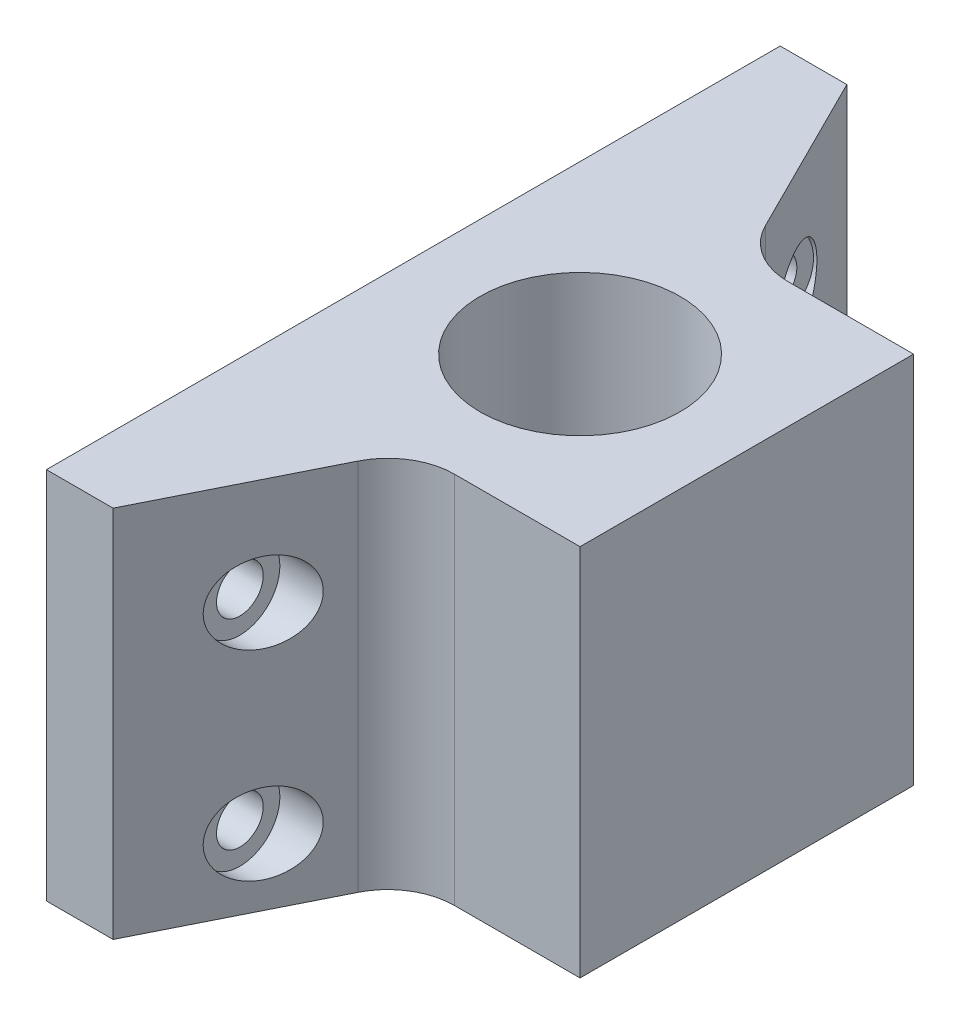
SolidWorks part; units mm, degrees
ref_plane "Front Plane" through (0, 0, 0) normal (0, 0, 1) x (1, 0, 0)
ref_plane "Top Plane" through (0, 0, 0) normal (0, 1, 0) x (1, 0, 0)
ref_plane "Right Plane" through (0, 0, 0) normal (1, 0, 0) x (0, 0, -1)
sketch "Sketch1" plane through (0, 0, 0) normal (0, 1, 0) x (1, 0, 0)
  line L1 (-12.5, 12.5) -> (12.5, 12.5)
  line L2 (-12.5, 12.5) -> (-12.5, -12.5)
  line L3 (-12.5, -12.5) -> (12.5, -12.5)
  line L4 (12.5, 12.5) -> (12.5, -12.5)
  line L5 (-12.5, 12.5) -> (12.5, -12.5) construction
  line L6 (-12.5, -12.5) -> (12.5, 12.5) construction
  point P0 (0, 0)
  dimension "D1" = 25
extrude "Boss-Extrude1" add sketch "Sketch1" along normal blind 28
sketch "Sketch2" plane through (0, 28, 0) normal (0, 1, 0) x (1, 0, 0)
  circle A0 centre (0, 0) radius 5
  dimension "D1" = 10
extrude "Cut-Extrude1" cut sketch "Sketch2" against normal blind 30
sketch "Sketch3" plane through (0, 28, 0) normal (0, 1, 0) x (1, 0, 0)
  circle A0 centre (0, 0) radius 7.5
  dimension "D1" = 15
extrude "Cut-Extrude2" cut sketch "Sketch3" against normal offset from surface (25 mm away) 3 up to face at (0, 0, 5)
sketch "Sketch6" plane through (0, 0, 0) normal (0, -1, 0) x (1, 0, 0)
  line L0 (-12.5, -12.5) -> (-12.5, -27.5)
  line L1 (-12.5, -12.5) -> (0, -12.5)
  line L2 (12.5, -12.5) -> (-12.5, -12.5) construction
  line L3 (-12.5, -27.5) -> (-7.5, -27.5)
  line L4 (-7.5, -27.5) -> (0, -12.5)
  line L5 (13.75, 0) -> (-13.75, 0) construction
  line L6 (-7.5, 27.5) -> (0, 12.5)
  line L7 (-12.5, 27.5) -> (-7.5, 27.5)
  line L8 (-12.5, 12.5) -> (0, 12.5)
  line L9 (-12.5, 12.5) -> (-12.5, 27.5)
  dimension "D1" = 15
  dimension "D2" = 5
extrude "Boss-Extrude2" add sketch "Sketch6" against normal up to surface (28 mm away) up to face at (0, 28, 7.5)
fillet "Fillet1" radius 5 2 edges at (0, 14, 12.5) (0, 14, -12.5)
sketch "Sketch7" plane through (-12.5, 0, 0) normal (-1, 0, 0) x (0, 0, 1)
  line L0 (0, 0) -> (0, 5) construction
  line L1 (0, 5) -> (20, 5) construction
  line L2 (20, 5) -> (20, 20) construction
  circle A0 centre (20, 20) radius 1.75
  circle A1 centre (20, 5) radius 1.75
  circle A2 centre (-20, 20) radius 1.75
  circle A3 centre (-20, 5) radius 1.75
  dimension "D4" = 3.5
  dimension "D5" = 3.5
  dimension "D1" = 5
  dimension "D2" = 20
  dimension "D3" = 15
extrude "Cut-Extrude3" cut sketch "Sketch7" against normal blind 13
sketch "Sketch8" plane through (12.5, 0, 0) normal (1, 0, 0) x (0, 0, -1)
  line L0 (0, 0) -> (0, 5) construction
  line L1 (0, 5) -> (20, 5) construction
  line L2 (20, 5) -> (20, 20) construction
  circle A0 centre (20, 20) radius 3
  circle A1 centre (20, 5) radius 3
  circle A2 centre (-20, 20) radius 3
  circle A3 centre (-20, 5) radius 3
  dimension "D1" = 5
  dimension "D4" = 6
  dimension "D5" = 6
  dimension "D2" = 20
  dimension "D3" = 15
extrude "Cut-Extrude4" cut sketch "Sketch8" against normal blind 18
